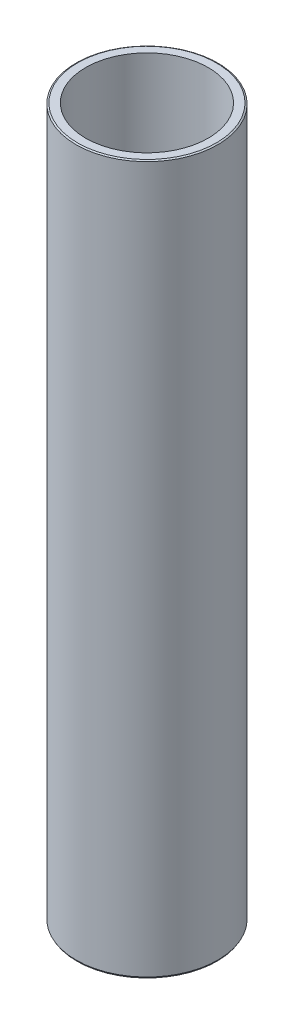
SolidWorks part; units mm, degrees
ref_plane "Front Plane" through (0, 0, 0) normal (0, 0, 1) x (1, 0, 0)
ref_plane "Top Plane" through (0, 0, 0) normal (0, 1, 0) x (1, 0, 0)
ref_plane "Right Plane" through (0, 0, 0) normal (1, 0, 0) x (0, 0, -1)
sketch "Sketch1" plane through (0, 0, 0) normal (0, 1, 0) x (1, 0, 0)
  circle A0 centre (0, 0) radius 60
  dimension "SHAFT_OD" = 120
extrude "Boss-Extrude1" add sketch "Sketch1" along normal blind 600
sketch "Sketch2" plane through (0, 0, 0) normal (0, 1, 0) x (1, 0, 0)
  circle A0 centre (0, 0) radius 51.8925
  dimension "BORE_D" = 103.785
extrude "Cut-Extrude1" cut sketch "Sketch2" along normal through all
chamfer "Chamfer1" distance 0.7197 angle 60 2 edges at (0, 600, 60) (0, 0, 60) first distance on face at (0, 600, 60) first distance on face at (0, 0, 51.8925)
